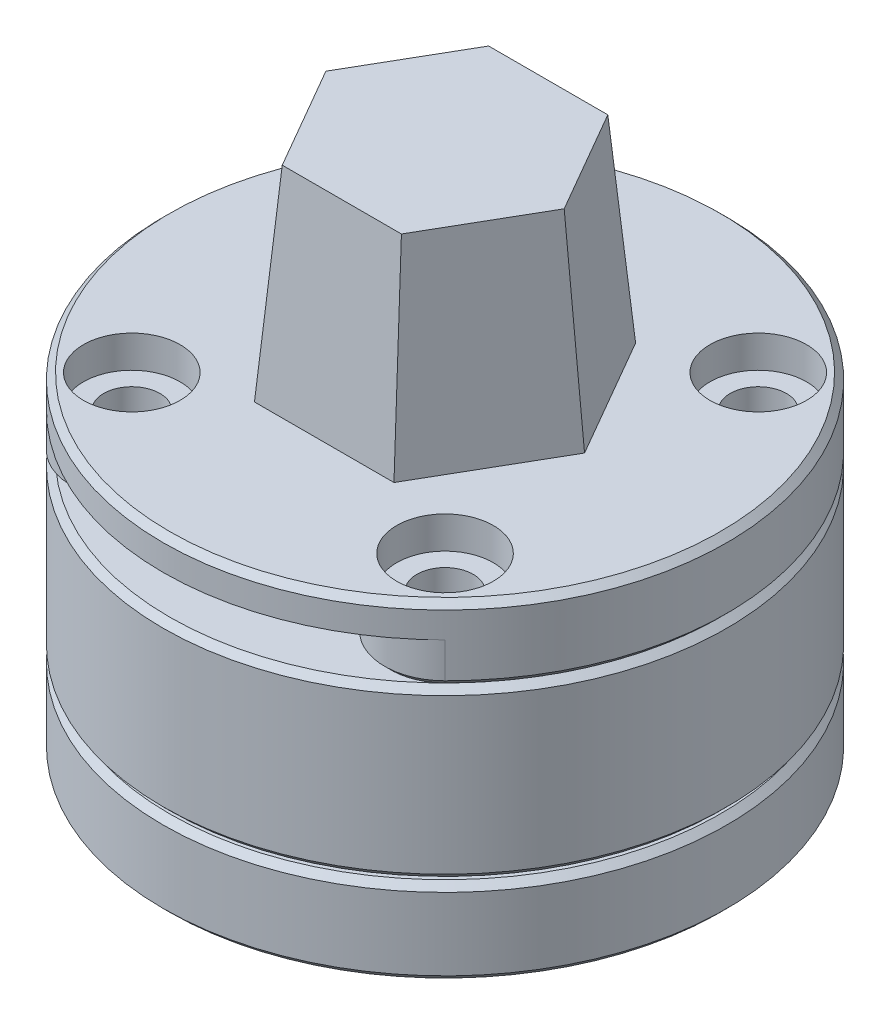
SolidWorks part; units mm, degrees
ref_plane "Front Plane" through (0, 0, 0) normal (0, 0, 1) x (1, 0, 0)
ref_plane "Top Plane" through (0, 0, 0) normal (0, 1, 0) x (1, 0, 0)
ref_plane "Right Plane" through (0, 0, 0) normal (1, 0, 0) x (0, 0, -1)
sketch "Sketch1" plane through (0, 0, 0) normal (0, 1, 0) x (1, 0, 0)
  circle A0 centre (0, 0) radius 17.5
  circle A1 centre (0, 0) radius 7.5 construction
  circle A2 centre (7.5, 0) radius 1.75
  circle A3 centre (0, 7.5) radius 1.75
  circle A4 centre (-7.5, 0) radius 1.75
  circle A5 centre (0, -7.5) radius 1.75
  dimension "D1" = 3.5
  dimension "D2" = 15
  dimension "D3" = 35
extrude "Main Boss" add sketch "Sketch1" along normal blind 5.287
sketch "Sketch3" plane through (0, 5.287, 0) normal (0, 1, 0) x (1, 0, 0)
  circle A0 centre (0, 0) radius 14.8987
  circle A2 centre (-7.5, 0) radius 1.75 construction
  circle A3 centre (0, -7.5) radius 1.75 construction
  circle A4 centre (7.5, 0) radius 1.75 construction
  circle A5 centre (0, 7.5) radius 1.75 construction
  circle A6 centre (-7.5, 0) radius 1.75
  circle A7 centre (0, -7.5) radius 1.75
  circle A8 centre (7.5, 0) radius 1.75
  circle A9 centre (0, 7.5) radius 1.75
  dimension "D1" = 29.7974
extrude "Codewheel Center Boss" add sketch "Sketch3" along normal blind 0.5
sketch "Sketch4" plane through (0, 5.287, 0) normal (0, 1, 0) x (1, 0, 0)
  circle A0 centre (0, 0) radius 16.5
  circle A1 centre (0, 0) radius 17.5 construction
  circle A2 centre (0, 0) radius 14.8987 construction
  circle A3 centre (0, 0) radius 14.8987
  dimension "D1" = 1
extrude "Codewheel Relief Cut" cut sketch "Sketch4" against normal blind 0.4
chamfer "Codewheel Relief Chamfer" distance 0.4 angle 45 1 edges at (0, 4.887, 16.5)
ref_plane "Plane1" through (0, 5.4648, 0) normal (0, 1, 0) x (1, 0, 0)
sketch "Sketch6" plane through (0, 5.4648, 0) normal (0, 1, 0) x (1, 0, 0)
  circle A0 centre (0, 0) radius 16.5 construction
  circle A1 centre (0, 0) radius 17.5 construction
  circle A2 centre (0, 0) radius 16.5
  circle A3 centre (0, 0) radius 17.5
extrude "Codewheel Top Boss" add sketch "Sketch6" along normal blind 0.4 separate body
sketch "Sketch7" plane through (0, 5.8648, 0) normal (0, 1, 0) x (1, 0, 0)
  circle A0 centre (0, 0) radius 17.5 construction
  circle A1 centre (0, 0) radius 17.5
  circle A2 centre (0, -7.5) radius 1.75 construction
  circle A3 centre (7.5, 0) radius 1.75 construction
  circle A4 centre (-7.5, 0) radius 1.75 construction
  circle A5 centre (0, 7.5) radius 1.75 construction
  circle A6 centre (0, -7.5) radius 1.75
  circle A7 centre (7.5, 0) radius 1.75
  circle A8 centre (-7.5, 0) radius 1.75
  circle A9 centre (0, 7.5) radius 1.75
extrude "Secondary Boss" add sketch "Sketch7" along normal blind 10
chamfer "Codewheel Relief Chamfer 2" distance 0.4 angle 45 1 edges at (0, 5.8648, 16.5)
sketch "Sketch8" plane through (0, 15.8648, 0) normal (0, 1, 0) x (1, 0, 0)
  circle A0 centre (-7.5, 0) radius 3
  circle A1 centre (0, 7.5) radius 3
  circle A2 centre (7.5, 0) radius 3
  circle A3 centre (0, -7.5) radius 3
  dimension "D1" = 6
extrude "Motor Bolt Countersinks" cut sketch "Sketch8" against normal blind 8
chamfer "Edge Chamfers 1" distance 0.4 angle 45 2 edges at (0, 0, 17.5) (0, 5.287, 17.5)
chamfer "Edge Chamfers 2" distance 0.4 angle 45 2 edges at (0, 15.8648, 17.5) (0, 5.4648, 17.5)
sketch "Sketch11" plane through (0, 15.8648, 0) normal (0, 1, 0) x (1, 0, 0)
  line L0 (0, 0) -> (0, -6.5) construction
  line L1 (-10.5, 5.5) -> (10.5, 5.5) construction
  line L2 (-10.5, 5.5) -> (-10.5, -6.5) construction
  line L3 (-10.5, -6.5) -> (10.5, -6.5) construction
  line L4 (10.5, 5.5) -> (10.5, -6.5) construction
  line L5 (-10.6, 5.6) -> (-10.6, -6.6)
  line L6 (-10.6, -6.6) -> (10.6, -6.6)
  line L7 (10.6, 5.6) -> (10.6, -6.6)
  line L8 (-10.6, 5.6) -> (10.6, 5.6)
  dimension "D1" = 21
  dimension "D2" = 6.5
  dimension "D3" = 5.5
  dimension "D4" = 0.1
extrude "Accelerometer Notch" cut sketch "Sketch11" against normal blind 1
sketch "Sketch12" plane through (0, 14.8648, 0) normal (0, 1, 0) x (1, 0, 0)
  line L0 (10.6, -6.6) -> (10.6, 5.6) construction
  line L1 (-10.6, -6.6) -> (10.6, -6.6)
  line L2 (-10.6, -6.6) -> (-10.6, -4.6)
  line L3 (-10.6, -4.6) -> (10.6, -4.6)
  line L4 (10.6, -6.6) -> (10.6, -4.6)
  dimension "D1" = 2
extrude "Accelerometer Pin Notch" cut sketch "Sketch12" against normal blind 1.6
fillet "Fillet1" radius 1 4 edges at (-2.8618, 14.5648, 6.6) (2.8618, 14.5648, 6.6) (-2.3216, 15.3648, -5.6) (2.3216, 15.3648, -5.6)
chamfer "Accelerometer Pin Notch Chamfer" distance 1.6 angle 45 2 edges at (-5.6841, 14.8648, 4.6) (5.6841, 14.8648, 4.6)
sketch "Sketch13" plane through (0, 15.8648, 0) normal (0, 1, 0) x (1, 0, 0)
  line L0 (-9.7227, 9.7227) -> (9.7227, -9.7227) construction
  line L1 (9.7227, -9.7227) -> (9.7227, 9.7227) construction
  line L2 (9.7227, 9.7227) -> (-9.7227, -9.7227) construction
  line L3 (-9.7227, -9.7227) -> (9.7227, -9.7227) construction
  circle A0 centre (0, 0) radius 13.75 construction
  circle A1 centre (9.7227, 9.7227) radius 2.35
  circle A2 centre (-9.7227, 9.7227) radius 2.35
  circle A3 centre (-9.7227, -9.7227) radius 2.35
  circle A4 centre (9.7227, -9.7227) radius 2.35
  dimension "D1" = 27.5
  dimension "D2" = 4.7
extrude "Accelerometer Layer Heat Set Insert Holes" cut sketch "Sketch13" against normal blind 4.2
sketch "Sketch14" plane through (0, 11.6648, 0) normal (0, 1, 0) x (1, 0, 0)
  circle A0 centre (-9.7227, 9.7227) radius 1.75
  circle A1 centre (9.7227, -9.7227) radius 1.75
  circle A2 centre (-9.7227, -9.7227) radius 1.75
  circle A3 centre (9.7227, 9.7227) radius 1.75
  circle A4 centre (9.7227, 9.7227) radius 2.35 construction
  dimension "D1" = 3.5
extrude "Accelerometer Layer Bolt Through Holes" cut sketch "Sketch14" against normal blind 5
sketch "Sketch15" plane through (0, 15.8648, 0) normal (0, 1, 0) x (1, 0, 0)
  line L0 (7.6464, -6.6) -> (10.6, -6.6)
  line L1 (-10.6, 5.6) -> (10.6, 5.6)
  line L2 (-10.6, 5.6) -> (-10.6, -6.6)
  line L3 (-10.6, -6.6) -> (-7.6464, -6.6)
  line L4 (10.6, 5.6) -> (10.6, -6.6)
  arc A0 (12.3744, -12.3744) -> (-12.3744, -12.3744) centre (0, 0) ccw
  circle A1 centre (0, 0) radius 17.5 construction
  circle A2 centre (-9.7227, -9.7227) radius 1.75 construction
  circle A3 centre (9.7227, -9.7227) radius 1.75 construction
  circle A4 centre (9.7227, 9.7227) radius 1.75 construction
  circle A5 centre (-9.7227, 9.7227) radius 1.75 construction
  circle A6 centre (-9.7227, -9.7227) radius 1.75
  circle A7 centre (9.7227, -9.7227) radius 1.75
  circle A8 centre (9.7227, 9.7227) radius 1.75
  circle A9 centre (-9.7227, 9.7227) radius 1.75
  arc A10 (-12.3744, -12.3744) -> (-7.6464, -6.6) centre (-9.7227, -9.7227) ccw
  arc A11 (7.6464, -6.6) -> (12.3744, -12.3744) centre (9.7227, -9.7227) ccw
extrude "Accelerometer Cover" add sketch "Sketch15" along normal blind 2.6 separate body
sketch "Sketch17" plane through (0, 18.4648, 0) normal (0, 1, 0) x (1, 0, 0)
  circle A0 centre (0, 0) radius 17.5
  arc A1 (12.3744, -12.3744) -> (-12.3744, -12.3744) centre (0, 0) ccw construction
  circle A2 centre (-9.7227, -9.7227) radius 1.75 construction
  circle A3 centre (-9.7227, 9.7227) radius 1.75 construction
  circle A4 centre (9.7227, 9.7227) radius 1.75 construction
  circle A5 centre (9.7227, -9.7227) radius 1.75 construction
  circle A6 centre (-9.7227, -9.7227) radius 1.75
  circle A7 centre (-9.7227, 9.7227) radius 1.75
  circle A8 centre (9.7227, 9.7227) radius 1.75
  circle A9 centre (9.7227, -9.7227) radius 1.75
extrude "Accelerometer Cover Boss" add sketch "Sketch17" along normal blind 2
sketch "Sketch19" plane through (0, 20.4648, 0) normal (0, 1, 0) x (1, 0, 0)
  circle A0 centre (-9.7227, 9.7227) radius 3
  circle A1 centre (9.7227, 9.7227) radius 3
  circle A2 centre (9.7227, -9.7227) radius 3
  circle A3 centre (-9.7227, -9.7227) radius 3
  dimension "D1" = 6
extrude "Acclerometer Cover Countersinks" cut sketch "Sketch19" against normal blind 2
chamfer "Edge Chamfers 3" distance 0.4 angle 45 4 edges at (0, 20.4648, 17.5) (6.8212, 15.8648, 12.0984) (-6.8212, 15.8648, 12.0984) (0, 15.8648, -17.5)
sketch "Sketch18" plane through (0, 20.4648, 0) normal (0, 1, 0) x (1, 0, 0)
  line L1 (4.3301, 7.5) -> (-4.3301, 7.5)
  line L2 (-4.3301, 7.5) -> (-8.6603, 0)
  line L3 (-8.6603, 0) -> (-4.3301, -7.5)
  line L4 (-4.3301, -7.5) -> (4.3301, -7.5)
  line L5 (4.3301, -7.5) -> (8.6603, 0)
  line L6 (8.6603, 0) -> (4.3301, 7.5)
  circle A0 centre (0, 0) radius 7.5 construction
  dimension "D1" = 15
extrude "Output Cone" add sketch "Sketch18" along normal blind 12.5 draft 5
